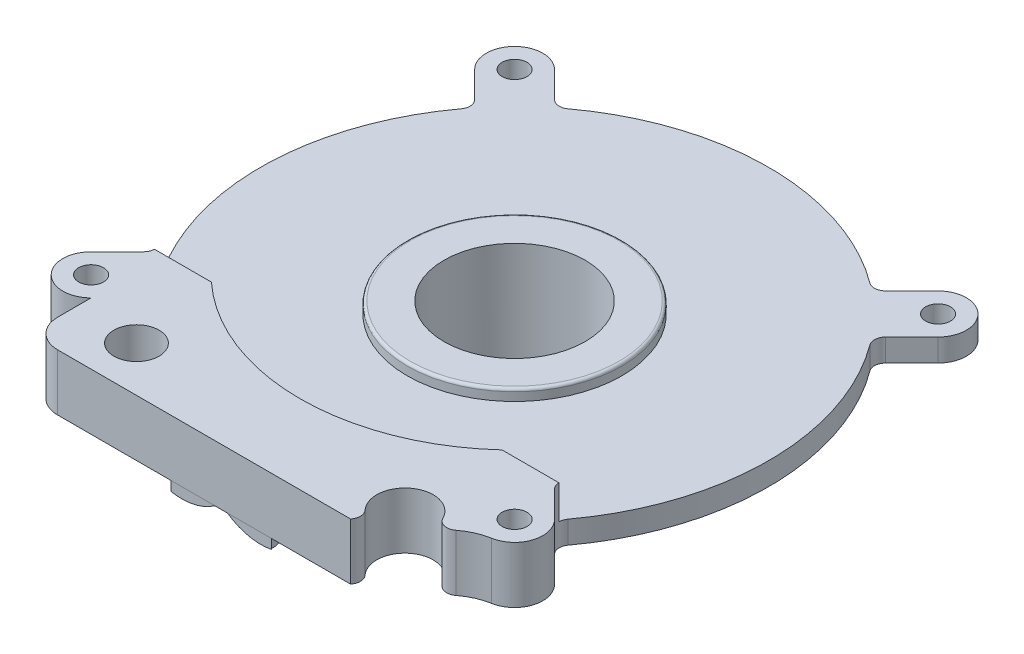
SolidWorks part; units mm, degrees
ref_plane "前视基准面" through (0, 0, 0) normal (0, 0, 1) x (1, 0, 0)
ref_plane "上视基准面" through (0, 0, 0) normal (0, 1, 0) x (1, 0, 0)
ref_plane "右视基准面" through (0, 0, 0) normal (1, 0, 0) x (0, 0, -1)
sketch "草图1" plane through (0, 0, 0) normal (0, 1, 0) x (1, 0, 0)
  circle A0 centre (0, 0) radius 12.5
  circle A1 centre (0, 0) radius 15
  dimension "D1" = 30
  dimension "D2" = 25
extrude "凸台-拉伸1" add sketch "草图1" along normal blind 20
sketch "草图2" plane through (0, 20, 0) normal (0, 1, 0) x (1, 0, 0)
  circle A0 centre (0, 0) radius 17
  circle A1 centre (0, 0) radius 12.5
  dimension "D1" = 34
  dimension "D2" = 25
extrude "凸台-拉伸2" add sketch "草图2" along normal blind 6
sketch "草图3" plane through (0, 0, 0) normal (0, -1, 0) x (1, 0, 0)
  line L0 (0, 0) -> (9.5, 0) construction
  circle A0 centre (0, 0) radius 7
  circle A2 centre (0, 0) radius 12.5
  circle A3 centre (9.5, 0) radius 1.65
  circle A4 centre (-4.75, -8.2272) radius 1.65
  circle A5 centre (-4.75, 8.2272) radius 1.65
  point P12 (0, 0)
  dimension "D1" = 14
  dimension "D2" = 25
  dimension "D3" = 3.3
  dimension "D4" = 9.5
  dimension "D5" = 3
extrude "凸台-拉伸3" add sketch "草图3" against normal blind 3
sketch "草图5" plane through (0, 26, 0) normal (0, 1, 0) x (1, 0, 0)
  line L1 (19, 19) -> (-19, 19)
  line L2 (19, 19) -> (19, -19)
  line L3 (19, -19) -> (-19, -19)
  line L4 (-19, 19) -> (-19, -19)
  line L5 (19, 19) -> (-19, -19) construction
  line L6 (19, -19) -> (-19, 19) construction
  circle A0 centre (0, 0) radius 19
  circle A1 centre (0, 0) radius 17
  point P0 (0, 0)
  circle M3 centre (0, 0) radius 17
  dimension "D3" = 34
  dimension "D1" = 38
  dimension "D2" = 38
extrude "凸台-拉伸5" add sketch "草图5" against normal blind 2 contours A0 M3 region at (13.055, 26, -13.055)
sketch "草图6" plane through (0, 26, 0) normal (0, 1, 0) x (1, 0, 0)
  line L1 (13, -13) -> (-13, -13)
  line L2 (13, -13) -> (13, 13)
  line L3 (13, 13) -> (-13, 13)
  line L4 (-13, -13) -> (-13, 13)
  line L5 (13, -13) -> (-13, 13) construction
  line L6 (13, 13) -> (-13, -13) construction
  circle A1 centre (0, 0) radius 12.5
  point P0 (0, 0)
  dimension "D2" = 25
  dimension "D1" = 90
  dimension "D3" = 26
extrude "凸台-拉伸6" add sketch "草图6" along normal blind 2
sketch "草图7" plane through (0, 24, 0) normal (0, -1, 0) x (1, 0, 0)
  circle A0 centre (0, 0) radius 17
  circle A1 centre (0, 0) radius 45
  dimension "D1" = 90
extrude "凸台-拉伸7" add sketch "草图7" along normal blind 4
sketch "草图8" plane through (0, 24, 0) normal (0, 1, 0) x (1, 0, 0)
  line L0 (-41.0355, -33.9645) -> (-35.1583, -28.0872)
  line L1 (-37.5, -37.5) -> (37.5, -37.5) construction
  line L2 (-37.5, -37.5) -> (-37.5, 37.5) construction
  line L3 (-37.5, 37.5) -> (37.5, 37.5) construction
  line L4 (37.5, -37.5) -> (37.5, 37.5) construction
  line L5 (-37.5, -37.5) -> (37.5, 37.5) construction
  line L6 (-37.5, 37.5) -> (37.5, -37.5) construction
  line L7 (-33.9645, -41.0355) -> (-28.0872, -35.1583)
  line L8 (-41.0355, 33.9645) -> (-35.1583, 28.0872)
  line L9 (-33.9645, 41.0355) -> (-28.0872, 35.1583)
  line L12 (28.0872, 35.1583) -> (33.9645, 41.0355)
  line L13 (35.1583, 28.0872) -> (41.0355, 33.9645)
  line L14 (35.1583, -28.0872) -> (41.0355, -33.9645)
  line L15 (28.0872, -35.1583) -> (33.9645, -41.0355)
  circle A0 centre (-37.5, 37.5) radius 2.2
  circle A1 centre (-37.5, -37.5) radius 2.2
  circle A2 centre (37.5, -37.5) radius 2.2
  circle A3 centre (37.5, 37.5) radius 2.2
  arc A4 (-33.9645, 41.0355) -> (-41.0355, 33.9645) centre (-37.5, 37.5) ccw
  arc A5 (-41.0355, -33.9645) -> (-33.9645, -41.0355) centre (-37.5, -37.5) ccw
  arc A6 (33.9645, -41.0355) -> (41.0355, -33.9645) centre (37.5, -37.5) ccw
  arc A7 (41.0355, 33.9645) -> (33.9645, 41.0355) centre (37.5, 37.5) ccw
  arc A8 (-28.0872, 35.1583) -> (-35.1583, 28.0872) centre (0, 0) ccw
  arc A9 (-35.1583, -28.0872) -> (-28.0872, -35.1583) centre (0, 0) ccw
  arc A10 (35.1583, 28.0872) -> (28.0872, 35.1583) centre (0, 0) ccw
  arc A11 (28.0872, -35.1583) -> (35.1583, -28.0872) centre (0, 0) ccw
  point P0 (0, 0)
  dimension "D3" = 4.4
  dimension "D4" = 10
  dimension "D5" = 45
  dimension "D1" = 75
  dimension "D2" = 75
extrude "凸台-拉伸8" add sketch "草图8" against normal up to surface (4 mm away) up to face at (0, 20, 15)
sketch "草图9" plane through (0, 24, 0) normal (0, 1, 0) x (1, 0, 0)
  line L0 (28.0872, -35.1583) -> (33.9645, -41.0355) construction
  line L1 (28.0872, -35.1583) -> (33.9645, -41.0355)
  line L2 (22.9064, -51.9624) -> (27.6497, -50.7984) construction
  line L3 (22.9064, -51.9624) -> (27.6497, -50.7984)
  line L4 (-33.9645, -41.0355) -> (-28.0872, -35.1583) construction
  line L5 (-33.9645, -41.0355) -> (-28.0872, -35.1583)
  line L6 (22.9064, -51.9624) -> (-33.9645, -51.9624)
  line L7 (-33.9645, -51.9624) -> (-33.9645, -41.0355)
  circle A1 centre (-23.0016, -43.9607) radius 4
  arc A2 (31.0086, -48.1213) -> (27.6497, -50.7984) centre (26.5148, -45.9289) ccw
  arc A4 (38.3693, -42.4239) -> (31.0459, -48.0431) centre (40.1079, -52.2716) ccw
  arc A5 (-28.0872, -35.1583) -> (28.0872, -35.1583) centre (0, 0) ccw construction
  arc A6 (-28.0872, -35.1583) -> (28.0872, -35.1583) centre (0, 0) ccw
  arc A10 (33.9645, -41.0355) -> (41.0355, -33.9645) centre (37.5, -37.5) ccw construction
  arc A11 (33.9645, -41.0355) -> (38.3693, -42.4239) centre (37.5, -37.5) ccw
  line M6 (-33.9645, -41.0355) -> (-28.0872, -35.1583)
  arc M7 (-28.0872, -35.1583) -> (28.0872, -35.1583) centre (0, 0) ccw
  line M8 (28.0872, -35.1583) -> (33.9645, -41.0355)
  arc M9 (33.9645, -41.0355) -> (41.0355, -33.9645) centre (37.5, -37.5) ccw
  dimension "D1" = 20
  dimension "D2" = 8
extrude "凸台-拉伸9" add sketch "草图9" against normal up to surface (4 mm away) contours A4 L7 L6 L3 A2 A1 M9 M8 M7 M6 region at (-2.8102, 24, 46.1844) up to face at (0, 20, 15)
fillet "圆角1" radius 2 2 edges at (31.0459, 22, 48.0431) (27.6497, 22, 50.7984)
sketch "草图10" plane through (0, 26, 0) normal (0, 1, 0) x (1, 0, 0)
  circle A0 centre (0, 0) radius 19
extrude "切除-拉伸1" cut sketch "草图10" along normal through all
fillet "圆角2" radius 0.5 1 edges at (0, 26, 19)
fillet "圆角3" radius 5 1 edges at (-33.9645, 22, 51.9624)
sketch "草图11" plane through (0, 0, 0) normal (0, -1, 0) x (1, 0, 0)
  circle A0 centre (-4.75, 8.2272) radius 3
  circle A1 centre (9.5, 0) radius 3
  circle A2 centre (-4.75, -8.2272) radius 3
  dimension "D1" = 6
extrude "切除-拉伸2" cut sketch "草图11" against normal blind 1.5
sketch "草图12" plane through (0, 20, 0) normal (0, -1, 0) x (1, 0, 0)
  circle A0 centre (0, 0) radius 15
  circle A1 centre (0, 0) radius 15.75
  dimension "D1" = 30
  dimension "D2" = 31.5
extrude "凸台-拉伸10" add sketch "草图12" along normal blind 1
sketch "草图13" plane through (0, 24, 0) normal (0, 1, 0) x (1, 0, 0)
  line L0 (-35.2577, -27.9624) -> (35.2577, -27.9624)
  line L8 (-33.9645, -41.0355) -> (-33.9645, -46.9624)
  line L9 (-28.9645, -51.9624) -> (22.9064, -51.9624)
  line L10 (41.0355, -33.9645) -> (35.1583, -28.0872)
  line L11 (35.1583, 28.0872) -> (41.0355, 33.9645)
  line L12 (33.9645, 41.0355) -> (28.0872, 35.1583)
  line L13 (-28.0872, 35.1583) -> (-33.9645, 41.0355)
  line L14 (-41.0355, 33.9645) -> (-35.1583, 28.0872)
  line L15 (-35.1583, -28.0872) -> (-41.0355, -33.9645)
  line L16 (-33.9645, -41.0355) -> (-33.9645, -46.9624)
  line L17 (-28.9645, -51.9624) -> (22.9064, -51.9624)
  line L18 (41.0355, -33.9645) -> (35.1583, -28.0872)
  line L23 (-35.1583, -28.0872) -> (-41.0355, -33.9645)
  arc A0 (-35.2577, -27.9624) -> (35.2577, -27.9624) centre (0, 0) ccw
  arc A3 (-25.7314, -27.9624) -> (25.7314, -27.9624) centre (0, 0) ccw
  arc A4 (35.1583, 28.0872) -> (28.0872, 35.1583) centre (0, 0) ccw
  arc A12 (-33.9645, -46.9624) -> (-28.9645, -51.9624) centre (-28.9645, -46.9624) ccw
  arc A13 (22.9064, -51.9624) -> (22.8419, -49.3216) centre (21.3728, -50.6786) ccw
  arc A14 (30.9802, -43.6793) -> (22.8419, -49.3216) centre (26.5148, -45.9289) ccw
  arc A15 (30.9802, -43.6793) -> (33.9899, -44.3614) centre (32.7663, -42.7794) ccw
  arc A16 (38.3693, -42.4239) -> (33.9899, -44.3614) centre (40.1079, -52.2716) ccw
  arc A17 (38.3693, -42.4239) -> (41.0355, -33.9645) centre (37.5, -37.5) ccw
  arc A18 (35.1583, -28.0872) -> (35.1583, 28.0872) centre (0, 0) ccw
  arc A19 (41.0355, 33.9645) -> (33.9645, 41.0355) centre (37.5, 37.5) ccw
  arc A20 (28.0872, 35.1583) -> (-28.0872, 35.1583) centre (0, 0) ccw
  arc A21 (-33.9645, 41.0355) -> (-41.0355, 33.9645) centre (-37.5, 37.5) ccw
  arc A22 (-35.1583, 28.0872) -> (-35.1583, -28.0872) centre (0, 0) ccw
  arc A23 (-41.0355, -33.9645) -> (-33.9645, -41.0355) centre (-37.5, -37.5) ccw
  arc A24 (-33.9645, -46.9624) -> (-28.9645, -51.9624) centre (-28.9645, -46.9624) ccw
  arc A25 (22.9064, -51.9624) -> (22.8419, -49.3216) centre (21.3728, -50.6786) ccw
  arc A26 (30.9802, -43.6793) -> (22.8419, -49.3216) centre (26.5148, -45.9289) ccw
  arc A27 (30.9802, -43.6793) -> (33.9899, -44.3614) centre (32.7663, -42.7794) ccw
  arc A28 (38.3693, -42.4239) -> (33.9899, -44.3614) centre (40.1079, -52.2716) ccw
  arc A29 (38.3693, -42.4239) -> (41.0355, -33.9645) centre (37.5, -37.5) ccw
  arc A30 (35.1583, -28.0872) -> (35.2577, -27.9624) centre (0, 0) ccw
  arc A34 (-35.2577, -27.9624) -> (-35.1583, -28.0872) centre (0, 0) ccw
  arc A35 (-41.0355, -33.9645) -> (-33.9645, -41.0355) centre (-37.5, -37.5) ccw
  line M22 (-33.9645, -41.0355) -> (-33.9645, -46.9624)
  arc M23 (-33.9645, -46.9624) -> (-28.9645, -51.9624) centre (-28.9645, -46.9624) ccw
  line M24 (-28.9645, -51.9624) -> (22.9064, -51.9624)
  arc M25 (22.9064, -51.9624) -> (22.8419, -49.3216) centre (21.3728, -50.6786) ccw
  arc M26 (22.8419, -49.3216) -> (30.9802, -43.6793) centre (26.5148, -45.9289) cw
  arc M27 (30.9802, -43.6793) -> (33.9899, -44.3614) centre (32.7663, -42.7794) ccw
  arc M28 (33.9899, -44.3614) -> (38.3693, -42.4239) centre (40.1079, -52.2716) cw
  arc M29 (38.3693, -42.4239) -> (41.0355, -33.9645) centre (37.5, -37.5) ccw
  line M30 (41.0355, -33.9645) -> (35.1583, -28.0872)
  arc M31 (35.1583, -28.0872) -> (35.1583, 28.0872) centre (0, 0) ccw
  arc M39 (-35.1583, 28.0872) -> (-35.1583, -28.0872) centre (0, 0) ccw
  line M40 (-35.1583, -28.0872) -> (-41.0355, -33.9645)
  arc M41 (-41.0355, -33.9645) -> (-33.9645, -41.0355) centre (-37.5, -37.5) ccw
  circle M42 centre (-37.5, -37.5) radius 2.2
  circle M45 centre (37.5, -37.5) radius 2.2
  circle M46 centre (-23.0016, -43.9607) radius 4
  dimension "D2" = 76
  dimension "D3" = 24
  dimension "D1" = 0
extrude "凸台-拉伸11" add sketch "草图13" along normal blind 4.2 contours A3 L0 A0 M39 M31 | A0 M40 M41 M22 M23 M24 M25 M26 M27 M28 M29 M30 M45 M46 M42 region at (-30.4946, 24, 28.6878) region at (0, 24, 45.8829)
sketch "草图14" plane through (0, 0, 51.9624) normal (0, 0, 1) x (1, 0, 0)
  line L0 (-8.9, 11.1) -> (-8.9, 20)
  line L1 (8.9, 11.1) -> (8.9, 20)
  line L4 (22.9064, 20) -> (22.9064, 28.2)
  line L5 (22.9064, 28.2) -> (-28.9645, 28.2)
  line L6 (-28.9645, 28.2) -> (-28.9645, 20)
  line L7 (-28.9645, 20) -> (22.9064, 20)
  line L8 (22.9064, 20) -> (22.9064, 28.2)
  line L9 (22.9064, 28.2) -> (-28.9645, 28.2)
  line L10 (-28.9645, 28.2) -> (-28.9645, 20)
  line L11 (-28.9645, 20) -> (22.9064, 20)
  circle A0 centre (0, 11.1) radius 8.9
  circle A1 centre (-7, 28.3) radius 10.1699
  circle A2 centre (7, 28.3) radius 10.1699
  circle A3 centre (0, 11.1) radius 8.4 construction
  line M8 (-28.9645, 20) -> (22.9064, 20)
  dimension "D2" = 17.8
  dimension "D3" = 7
  dimension "D6" = 16.8
  dimension "D4" = 7
  dimension "D5" = 17.2
  dimension "D1" = 0
extrude "凸台-拉伸12" add sketch "草图14" against normal blind 7 separate body contours L0 A1 A0 M8 | A0 A1 | A2 A0 L1 M8 | A0 A2 region at (-6.148, 19.2116, 51.9624) region at (-3.2594, 19.1088, 51.9624) region at (6.148, 19.2116, 51.9624) region at (3.2594, 19.1088, 51.9624)
chamfer "倒角1" distance 1.9 angle 73 1 edges at (4.8394, 18.3623, 44.9624) first distance on face at (6.2503, 19.1723, 44.9624)
chamfer "倒角2" distance 1.9 angle 73 1 edges at (-4.8394, 18.3623, 44.9624) first distance on face at (-6.2503, 19.1723, 44.9624)
sketch "草图15" plane through (0, 20, 0) normal (0, -1, 0) x (1, 0, 0)
  line L0 (8.75, 51.9615) -> (12.7263, 51.9624)
  line L1 (-28.9645, 51.9624) -> (22.9064, 51.9624) construction
  line L2 (12.7263, 51.9624) -> (6.3302, 38.4828)
  circle A0 centre (-30, 51.9615) radius 38.75
  dimension "D1" = 77.5
extrude "切除-拉伸4" cut sketch "草图15" along normal blind 10 contours A0 L2 L0 region at (9.6599, 20, 48.0705)
fillet "圆角4" radius 2 6 edges at (-35.1583, 24.1, 28.0872) (35.1583, 22, -28.0872) (28.0872, 22, -35.1583) (-28.0872, 22, -35.1583) (-35.1583, 22, -28.0872) (35.1583, 24.1, 28.0872)
sketch "草图16" plane through (0, 28.2, 0) normal (0, 1, 0) x (1, 0, 0)
  line L6 (-25.7314, -27.9624) -> (-35.8137, -27.9624)
  line L7 (-36.3989, -29.3278) -> (-41.0355, -33.9645)
  line L8 (-33.9645, -41.0355) -> (-33.9645, -46.9624)
  line L9 (-28.9645, -51.9624) -> (22.9064, -51.9624)
  line L10 (41.0355, -33.9645) -> (36.3989, -29.3278)
  line L11 (35.8137, -27.9624) -> (25.7314, -27.9624)
  line L12 (-25.7314, -27.9624) -> (-35.8137, -27.9624)
  line L13 (-36.3989, -29.3278) -> (-41.0355, -33.9645)
  line L14 (-33.9645, -41.0355) -> (-33.9645, -46.9624)
  line L15 (-28.9645, -51.9624) -> (22.9064, -51.9624)
  line L16 (41.0355, -33.9645) -> (36.3989, -29.3278)
  line L17 (35.8137, -27.9624) -> (25.7314, -27.9624)
  circle A0 centre (-37.5, -37.5) radius 2.2
  circle A1 centre (-23.0016, -43.9607) radius 4
  circle A2 centre (37.5, -37.5) radius 2.2
  arc A10 (-25.7314, -27.9624) -> (25.7314, -27.9624) centre (0, 0) ccw
  arc A11 (-36.3989, -29.3278) -> (-35.8137, -27.9624) centre (-37.8131, -27.9136) ccw
  arc A12 (-41.0355, -33.9645) -> (-33.9645, -41.0355) centre (-37.5, -37.5) ccw
  arc A13 (-33.9645, -46.9624) -> (-28.9645, -51.9624) centre (-28.9645, -46.9624) ccw
  arc A14 (22.9064, -51.9624) -> (22.8419, -49.3216) centre (21.3728, -50.6786) ccw
  arc A15 (30.9802, -43.6793) -> (22.8419, -49.3216) centre (26.5148, -45.9289) ccw
  arc A16 (30.9802, -43.6793) -> (33.9899, -44.3614) centre (32.7663, -42.7794) ccw
  arc A17 (38.3693, -42.4239) -> (33.9899, -44.3614) centre (40.1079, -52.2716) ccw
  arc A18 (38.3693, -42.4239) -> (41.0355, -33.9645) centre (37.5, -37.5) ccw
  arc A19 (35.8137, -27.9624) -> (36.3989, -29.3278) centre (37.8131, -27.9136) ccw
  arc A20 (-25.7314, -27.9624) -> (25.7314, -27.9624) centre (0, 0) ccw
  arc A21 (-36.3989, -29.3278) -> (-35.8137, -27.9624) centre (-37.8131, -27.9136) ccw
  arc A22 (-41.0355, -33.9645) -> (-33.9645, -41.0355) centre (-37.5, -37.5) ccw
  arc A23 (-33.9645, -46.9624) -> (-28.9645, -51.9624) centre (-28.9645, -46.9624) ccw
  arc A24 (22.9064, -51.9624) -> (22.8419, -49.3216) centre (21.3728, -50.6786) ccw
  arc A25 (30.9802, -43.6793) -> (22.8419, -49.3216) centre (26.5148, -45.9289) ccw
  arc A26 (30.9802, -43.6793) -> (33.9899, -44.3614) centre (32.7663, -42.7794) ccw
  arc A27 (38.3693, -42.4239) -> (33.9899, -44.3614) centre (40.1079, -52.2716) ccw
  arc A28 (38.3693, -42.4239) -> (41.0355, -33.9645) centre (37.5, -37.5) ccw
  arc A29 (35.8137, -27.9624) -> (36.3989, -29.3278) centre (37.8131, -27.9136) ccw
  dimension "D1" = 0
extrude "凸台-拉伸13" add sketch "草图16" along normal blind 3
sketch "草图17" plane through (0, 31.2, 0) normal (0, 1, 0) x (1, 0, 0)
  line L6 (-25.7314, -27.9624) -> (-35.8137, -27.9624)
  line L7 (-36.3989, -29.3278) -> (-41.0355, -33.9645)
  line L8 (-33.9645, -41.0355) -> (-33.9645, -46.9624)
  line L9 (-28.9645, -51.9624) -> (22.9064, -51.9624)
  line L10 (41.0355, -33.9645) -> (36.3989, -29.3278)
  line L11 (35.8137, -27.9624) -> (25.7314, -27.9624)
  line L12 (-25.7314, -27.9624) -> (-35.8137, -27.9624)
  line L13 (-36.3989, -29.3278) -> (-41.0355, -33.9645)
  line L14 (-33.9645, -41.0355) -> (-33.9645, -46.9624)
  line L15 (-28.9645, -51.9624) -> (22.9064, -51.9624)
  line L16 (41.0355, -33.9645) -> (36.3989, -29.3278)
  line L17 (35.8137, -27.9624) -> (25.7314, -27.9624)
  arc A10 (-25.7314, -27.9624) -> (25.7314, -27.9624) centre (0, 0) ccw
  arc A11 (-36.3989, -29.3278) -> (-35.8137, -27.9624) centre (-37.8131, -27.9136) ccw
  arc A12 (-41.0355, -33.9645) -> (-33.9645, -41.0355) centre (-37.5, -37.5) ccw
  arc A13 (-33.9645, -46.9624) -> (-28.9645, -51.9624) centre (-28.9645, -46.9624) ccw
  arc A14 (22.9064, -51.9624) -> (22.8419, -49.3216) centre (21.3728, -50.6786) ccw
  arc A15 (30.9802, -43.6793) -> (22.8419, -49.3216) centre (26.5148, -45.9289) ccw
  arc A16 (30.9802, -43.6793) -> (33.9899, -44.3614) centre (32.7663, -42.7794) ccw
  arc A17 (38.3693, -42.4239) -> (33.9899, -44.3614) centre (40.1079, -52.2716) ccw
  arc A18 (38.3693, -42.4239) -> (41.0355, -33.9645) centre (37.5, -37.5) ccw
  arc A19 (35.8137, -27.9624) -> (36.3989, -29.3278) centre (37.8131, -27.9136) ccw
  arc A20 (-25.7314, -27.9624) -> (25.7314, -27.9624) centre (0, 0) ccw
  arc A21 (-36.3989, -29.3278) -> (-35.8137, -27.9624) centre (-37.8131, -27.9136) ccw
  arc A22 (-41.0355, -33.9645) -> (-33.9645, -41.0355) centre (-37.5, -37.5) ccw
  arc A23 (-33.9645, -46.9624) -> (-28.9645, -51.9624) centre (-28.9645, -46.9624) ccw
  arc A24 (22.9064, -51.9624) -> (22.8419, -49.3216) centre (21.3728, -50.6786) ccw
  arc A25 (30.9802, -43.6793) -> (22.8419, -49.3216) centre (26.5148, -45.9289) ccw
  arc A26 (30.9802, -43.6793) -> (33.9899, -44.3614) centre (32.7663, -42.7794) ccw
  arc A27 (38.3693, -42.4239) -> (33.9899, -44.3614) centre (40.1079, -52.2716) ccw
  arc A28 (38.3693, -42.4239) -> (41.0355, -33.9645) centre (37.5, -37.5) ccw
  arc A29 (35.8137, -27.9624) -> (36.3989, -29.3278) centre (37.8131, -27.9136) ccw
  dimension "D1" = 0
extrude "切除-拉伸5" cut sketch "草图17" against normal blind 0.2
sketch "草图18" plane through (0, 0, 51.9624) normal (0, 0, 1) x (1, 0, 0)
  line L0 (-28.9645, 31) -> (22.9064, 31) construction
  line L1 (-59.4354, 30) -> (59.4354, 30)
  line L2 (-59.4354, 30) -> (-59.4354, 32)
  line L3 (-59.4354, 32) -> (59.4354, 32)
  line L4 (59.4354, 30) -> (59.4354, 32)
  line L5 (-59.4354, 30) -> (59.4354, 32) construction
  line L6 (-59.4354, 32) -> (59.4354, 30) construction
  line L7 (42.5, 31) -> (38.3693, 31) construction
  point P0 (0, 31)
  dimension "D1" = 1
extrude "切除-拉伸6" cut sketch "草图18" against normal through all both and the other way through all
